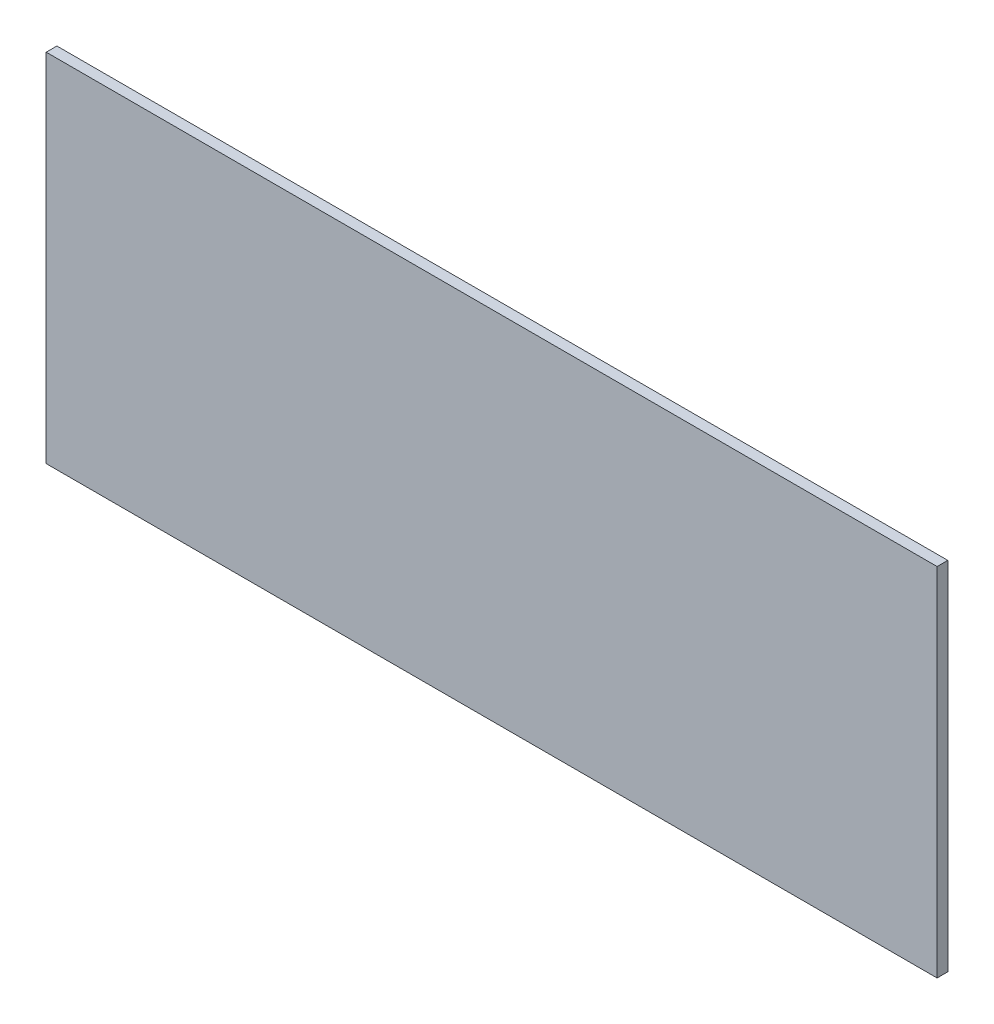
SolidWorks part; units mm, degrees
ref_plane "Ön Düzlem" through (0, 0, 0) normal (0, 0, 1) x (1, 0, 0)
ref_plane "Üst Düzlem" through (0, 0, 0) normal (0, 1, 0) x (1, 0, 0)
ref_plane "Sağ Düzlem" through (0, 0, 0) normal (1, 0, 0) x (0, 0, -1)
sketch "Çizim1" plane through (0, 0, 0) normal (0, 0, 1) x (1, 0, 0)
  line L1 (0, 0) -> (1000, 0)
  line L2 (0, 0) -> (0, -400)
  line L3 (0, -400) -> (1000, -400)
  line L4 (1000, 0) -> (1000, -400)
  dimension "D1" = 1000
  dimension "D2" = 400
base flange "Taban-Flanş1" sketch "Çizim1" thickness 12 reverse thickness direction no parameters "D1"=2.5
sketch "Büküm-Çizgileri1" [suppressed] plane through (0, 0, 0) normal (0, 1, 0) x (1, 0, 0)
sketch "Sınırlandırma-Kutusu1" [suppressed] plane through (0, 0, 0) normal (0, 1, 0) x (1, 0, 0)
sheet metal parameters "Sac-Levha1" thickness 12 parameters "D1"=2.5
flat pattern "Düz-Çoğaltma1" [suppressed]
sketch "Büküm-Çizgileri2" plane through (0, 0, 0) normal (0, 1, 0) x (1, 0, 0)
sketch3d "Sınırlandırma-Kutusu2" [suppressed]
  line L0 (0, -400, 0) -> (1000, -400, 0) construction
  line L1 (0, 0, 0) -> (1000, 0, 0) construction
  line L2 (0, -400, 0) -> (0, 0, 0) construction
  line L3 (1000, -400, 0) -> (1000, 0, 0) construction
